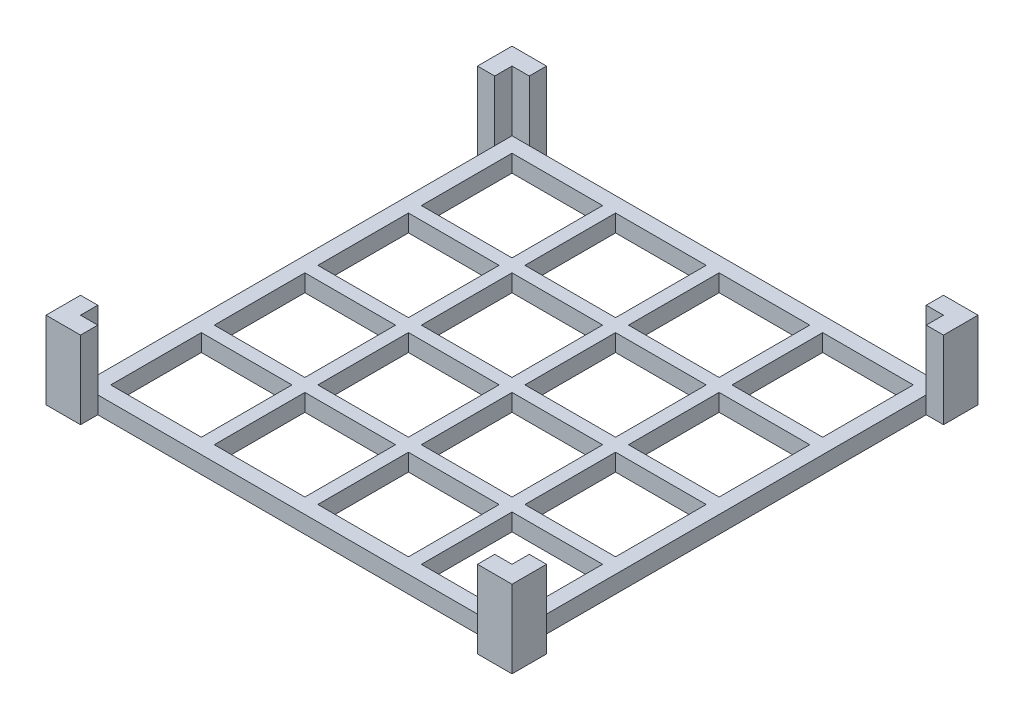
SolidWorks part; units mm, degrees
ref_plane "Front Plane" through (0, 0, 0) normal (0, 0, 1) x (1, 0, 0)
ref_plane "Top Plane" through (0, 0, 0) normal (0, 1, 0) x (1, 0, 0)
ref_plane "Right Plane" through (0, 0, 0) normal (1, 0, 0) x (0, 0, -1)
sketch "Sketch1" plane through (0, 0, 0) normal (0, 1, 0) x (1, 0, 0)
  line L1 (-42, 31) -> (-42, 33)
  line L2 (-42, 33) -> (-46, 33)
  line L3 (-46, 33) -> (-46, 29)
  line L4 (-46, 29) -> (-44, 29)
  line L5 (-44, 29) -> (-44, 31)
  line L6 (4, 33) -> (4, 31)
  line L7 (4, 31) -> (6, 31)
  line L8 (6, 29) -> (8, 29)
  line L9 (-19.75, 29.25) -> (-30.25, 29.25)
  line L10 (-19.75, 29.25) -> (-19.75, 18.75)
  line L11 (-19.75, 18.75) -> (-30.25, 18.75)
  line L12 (-30.25, 29.25) -> (-30.25, 18.75)
  line L13 (-19.75, 29.25) -> (-30.25, 18.75) construction
  line L14 (-19.75, 18.75) -> (-30.25, 29.25) construction
  line L15 (-31.75, 17.25) -> (-42.25, 17.25)
  line L16 (-31.75, 17.25) -> (-31.75, 6.75)
  line L17 (8, 29) -> (8, 33)
  line L18 (-42, 29) -> (-32, 29) construction
  line L19 (-42, 29) -> (-42, 19) construction
  line L20 (-42, 19) -> (-32, 19) construction
  line L21 (-32, 29) -> (-32, 19) construction
  line L22 (-30, 29) -> (-20, 29) construction
  line L23 (-30, 29) -> (-30, 19) construction
  line L24 (-30, 19) -> (-20, 19) construction
  line L25 (-20, 29) -> (-20, 19) construction
  line L26 (-18, 29) -> (-8, 29) construction
  line L27 (-18, 29) -> (-18, 19) construction
  line L28 (-18, 19) -> (-8, 19) construction
  line L29 (-8, 29) -> (-8, 19) construction
  line L30 (-6, 29) -> (4, 29) construction
  line L31 (-6, 29) -> (-6, 19) construction
  line L32 (-6, 19) -> (4, 19) construction
  line L33 (4, 29) -> (4, 19) construction
  line L34 (-32, 17) -> (-42, 17) construction
  line L35 (-32, 17) -> (-32, 7) construction
  line L36 (-32, 7) -> (-42, 7) construction
  line L37 (-42, 17) -> (-42, 7) construction
  line L38 (-30, 17) -> (-20, 17) construction
  line L39 (-30, 17) -> (-30, 7) construction
  line L40 (-30, 7) -> (-20, 7) construction
  line L41 (-20, 17) -> (-20, 7) construction
  line L42 (-18, 7) -> (-8, 7) construction
  line L43 (-18, 7) -> (-18, 17) construction
  line L44 (-18, 17) -> (-8, 17) construction
  line L45 (-8, 7) -> (-8, 17) construction
  line L46 (-6, 17) -> (4, 17) construction
  line L47 (-6, 17) -> (-6, 7) construction
  line L48 (-6, 7) -> (4, 7) construction
  line L49 (4, 17) -> (4, 7) construction
  line L50 (-6, 5) -> (4, 5) construction
  line L51 (-6, 5) -> (-6, -5) construction
  line L52 (-6, -5) -> (4, -5) construction
  line L53 (4, 5) -> (4, -5) construction
  line L54 (-18, -5) -> (-8, -5) construction
  line L55 (-18, -5) -> (-18, 5) construction
  line L56 (-18, 5) -> (-8, 5) construction
  line L57 (-8, -5) -> (-8, 5) construction
  line L58 (-20, 5) -> (-30, 5) construction
  line L59 (-20, 5) -> (-20, -5) construction
  line L60 (-20, -5) -> (-30, -5) construction
  line L61 (-30, 5) -> (-30, -5) construction
  line L62 (-32, -5) -> (-42, -5) construction
  line L63 (-32, -5) -> (-32, 5) construction
  line L64 (-32, 5) -> (-42, 5) construction
  line L65 (-42, -5) -> (-42, 5) construction
  line L66 (-42, -7) -> (-32, -7) construction
  line L67 (-42, -7) -> (-42, -17) construction
  line L68 (-42, -17) -> (-32, -17) construction
  line L69 (-32, -7) -> (-32, -17) construction
  line L70 (-30, -7) -> (-20, -7) construction
  line L71 (-30, -7) -> (-30, -17) construction
  line L72 (-30, -17) -> (-20, -17) construction
  line L73 (-20, -7) -> (-20, -17) construction
  line L74 (-18, -7) -> (-8, -7) construction
  line L75 (-18, -7) -> (-18, -17) construction
  line L76 (-18, -17) -> (-8, -17) construction
  line L77 (-8, -7) -> (-8, -17) construction
  line L78 (-6, -7) -> (4, -7) construction
  line L79 (-6, -7) -> (-6, -17) construction
  line L80 (-6, -17) -> (4, -17) construction
  line L81 (4, -7) -> (4, -17) construction
  line L82 (-44, 31) -> (6, 31)
  line L83 (-44, 31) -> (-44, -19)
  line L84 (-44, -19) -> (6, -19)
  line L85 (6, 31) -> (6, -19)
  line L86 (8, 33) -> (4, 33)
  line L87 (4, -19) -> (4, -21)
  line L88 (4, -21) -> (8, -21)
  line L89 (8, -21) -> (8, -17)
  line L90 (8, -17) -> (6, -17)
  line L91 (6, -17) -> (6, -19)
  line L92 (-42, -21) -> (-46, -21)
  line L93 (-46, -21) -> (-46, -17)
  line L94 (-46, -17) -> (-44, -17)
  line L95 (-44, -17) -> (-44, -19)
  line L96 (-42, -19) -> (-42, -21)
  line L97 (-31.75, 6.75) -> (-42.25, 6.75)
  line L98 (-31.75, 29.25) -> (-42.25, 29.25)
  line L99 (-31.75, 29.25) -> (-31.75, 18.75)
  line L100 (-31.75, 18.75) -> (-42.25, 18.75)
  line L101 (-42.25, 29.25) -> (-42.25, 18.75)
  line L102 (-42.25, 17.25) -> (-42.25, 6.75)
  line L103 (-31.75, 17.25) -> (-42.25, 6.75) construction
  line L104 (-31.75, 6.75) -> (-42.25, 17.25) construction
  line L105 (-7.75, 29.25) -> (-18.25, 29.25)
  line L106 (-7.75, 29.25) -> (-7.75, 18.75)
  line L107 (-7.75, 18.75) -> (-18.25, 18.75)
  line L108 (-18.25, 29.25) -> (-18.25, 18.75)
  line L109 (-7.75, 29.25) -> (-18.25, 18.75) construction
  line L110 (-7.75, 18.75) -> (-18.25, 29.25) construction
  line L111 (4.25, 29.25) -> (-6.25, 29.25)
  line L112 (4.25, 29.25) -> (4.25, 18.75)
  line L113 (4.25, 18.75) -> (-6.25, 18.75)
  line L114 (-6.25, 29.25) -> (-6.25, 18.75)
  line L115 (4.25, 29.25) -> (-6.25, 18.75) construction
  line L116 (4.25, 18.75) -> (-6.25, 29.25) construction
  line L117 (-31.75, 5.25) -> (-42.25, 5.25)
  line L118 (-31.75, 5.25) -> (-31.75, -5.25)
  line L119 (-31.75, -5.25) -> (-42.25, -5.25)
  line L120 (-42.25, 5.25) -> (-42.25, -5.25)
  line L121 (-31.75, 5.25) -> (-42.25, -5.25) construction
  line L122 (-31.75, -5.25) -> (-42.25, 5.25) construction
  line L123 (-31.75, -6.75) -> (-42.25, -6.75)
  line L124 (-31.75, -6.75) -> (-31.75, -17.25)
  line L125 (-31.75, -17.25) -> (-42.25, -17.25)
  line L126 (-42.25, -6.75) -> (-42.25, -17.25)
  line L127 (-31.75, -6.75) -> (-42.25, -17.25) construction
  line L128 (-31.75, -17.25) -> (-42.25, -6.75) construction
  line L129 (-19.75, 17.25) -> (-30.25, 17.25)
  line L130 (-19.75, 17.25) -> (-19.75, 6.75)
  line L131 (-19.75, 6.75) -> (-30.25, 6.75)
  line L132 (-30.25, 17.25) -> (-30.25, 6.75)
  line L133 (-19.75, 17.25) -> (-30.25, 6.75) construction
  line L134 (-19.75, 6.75) -> (-30.25, 17.25) construction
  line L135 (-19.75, 5.25) -> (-30.25, 5.25)
  line L136 (-19.75, 5.25) -> (-19.75, -5.25)
  line L137 (-19.75, -5.25) -> (-30.25, -5.25)
  line L138 (-30.25, 5.25) -> (-30.25, -5.25)
  line L139 (-19.75, 5.25) -> (-30.25, -5.25) construction
  line L140 (-19.75, -5.25) -> (-30.25, 5.25) construction
  line L141 (-7.75, 17.25) -> (-18.25, 17.25)
  line L142 (-7.75, 17.25) -> (-7.75, 6.75)
  line L143 (-7.75, 6.75) -> (-18.25, 6.75)
  line L144 (-18.25, 17.25) -> (-18.25, 6.75)
  line L145 (-7.75, 17.25) -> (-18.25, 6.75) construction
  line L146 (-7.75, 6.75) -> (-18.25, 17.25) construction
  line L147 (4.25, 17.25) -> (-6.25, 17.25)
  line L148 (4.25, 17.25) -> (4.25, 6.75)
  line L149 (4.25, 6.75) -> (-6.25, 6.75)
  line L150 (-6.25, 17.25) -> (-6.25, 6.75)
  line L151 (4.25, 17.25) -> (-6.25, 6.75) construction
  line L152 (4.25, 6.75) -> (-6.25, 17.25) construction
  line L153 (-7.75, 5.25) -> (-18.25, 5.25)
  line L154 (-7.75, 5.25) -> (-7.75, -5.25)
  line L155 (-7.75, -5.25) -> (-18.25, -5.25)
  line L156 (-18.25, 5.25) -> (-18.25, -5.25)
  line L157 (-7.75, 5.25) -> (-18.25, -5.25) construction
  line L158 (-7.75, -5.25) -> (-18.25, 5.25) construction
  line L159 (4.25, 5.25) -> (-6.25, 5.25)
  line L160 (4.25, 5.25) -> (4.25, -5.25)
  line L161 (4.25, -5.25) -> (-6.25, -5.25)
  line L162 (-6.25, 5.25) -> (-6.25, -5.25)
  line L163 (4.25, 5.25) -> (-6.25, -5.25) construction
  line L164 (4.25, -5.25) -> (-6.25, 5.25) construction
  line L165 (-19.75, -6.75) -> (-30.25, -6.75)
  line L166 (-19.75, -6.75) -> (-19.75, -17.25)
  line L167 (-19.75, -17.25) -> (-30.25, -17.25)
  line L168 (-30.25, -6.75) -> (-30.25, -17.25)
  line L169 (-19.75, -6.75) -> (-30.25, -17.25) construction
  line L170 (-19.75, -17.25) -> (-30.25, -6.75) construction
  line L171 (-7.75, -6.75) -> (-18.25, -6.75)
  line L172 (-7.75, -6.75) -> (-7.75, -17.25)
  line L173 (-7.75, -17.25) -> (-18.25, -17.25)
  line L174 (-18.25, -6.75) -> (-18.25, -17.25)
  line L175 (-7.75, -6.75) -> (-18.25, -17.25) construction
  line L176 (-7.75, -17.25) -> (-18.25, -6.75) construction
  line L177 (4.25, -6.75) -> (-6.25, -6.75)
  line L178 (4.25, -6.75) -> (4.25, -17.25)
  line L179 (4.25, -17.25) -> (-6.25, -17.25)
  line L180 (-6.25, -6.75) -> (-6.25, -17.25)
  line L181 (4.25, -6.75) -> (-6.25, -17.25) construction
  line L182 (4.25, -17.25) -> (-6.25, -6.75) construction
  point P1 (-12, 12)
  point P3 (-12, 0)
  point P8 (-24, 0)
  point P10 (0, 24)
  point P11 (-24, 12)
  point P12 (0, 12)
  point P13 (0, -12)
  point P14 (-12, -12)
  point P16 (-24, -12)
  point P19 (-36, 12)
  point P21 (-36, 24)
  point P22 (-24, 24)
  point P23 (-12, 24)
  point P24 (-36, 0)
  point P25 (-36, -12)
  point P26 (-25, 24)
  point P28 (-13, 24)
  point P32 (8, 29)
  point P34 (4, 33)
  point P35 (8, 33)
  point P36 (-46, -19)
  point P37 (-46, -21)
  point P38 (-42, -21)
  point P39 (4, -21)
  point P40 (8, -21)
  point P41 (8, -17)
  point P48 (-1, 24)
  point P49 (-13, 12)
  point P50 (-1, 12)
  point P51 (-25, 12)
  point P52 (-37, 12)
  point P54 (-37, 0)
  point P55 (-25, 0)
  point P56 (-13, 0)
  point P60 (-1, 0)
  point P62 (-1, -12)
  point P63 (-13, -12)
  point P64 (-25, -12)
  point P65 (-37, -12)
  point P66 (-25, 24)
  point P136 (-37, 12)
  point P144 (-13, 24)
  point P149 (-1, 24)
  point P154 (-37, 0)
  point P159 (-37, -12)
  point P164 (-25, 12)
  point P169 (-25, 0)
  point P174 (-13, 12)
  point P179 (-1, 12)
  point P184 (-13, 0)
  point P189 (-1, 0)
  point P194 (-25, -12)
  point P199 (-13, -12)
  point P204 (-1, -12)
  line B0 (-0.1035, 1.9813) -> (-3.7918, 1.315) construction
  line B1 (-3.7918, -1.315) -> (-0.1035, -1.9813) construction
  arc B2 (-3.9397, 1.2764) -> (-3.9397, -1.2764) centre (-3.5, 0) ccw construction
  arc B3 (0.1486, 1.9945) -> (0.1486, -1.9945) centre (0, 0) cw construction
  arc B4 (-3.9397, 1.2764) -> (-3.7918, 1.315) centre (-3.614, 0.3309) cw construction
  arc B5 (-3.7918, -1.315) -> (-3.9397, -1.2764) centre (-3.614, -0.3309) cw construction
  arc B6 (0.1486, 1.9945) -> (-0.1035, 1.9813) centre (0.0743, 0.9972) ccw construction
  arc B7 (0.1486, -1.9945) -> (-0.1035, -1.9813) centre (0.0743, -0.9972) cw construction
  line B8 (-12.1035, 1.9813) -> (-15.7918, 1.315) construction
  line B9 (-15.7918, -1.315) -> (-12.1035, -1.9813) construction
  arc B10 (-15.9397, 1.2764) -> (-15.9397, -1.2764) centre (-15.5, 0) ccw construction
  arc B11 (-11.8514, 1.9945) -> (-11.8514, -1.9945) centre (-12, 0) cw construction
  arc B12 (-15.9397, 1.2764) -> (-15.7918, 1.315) centre (-15.614, 0.3309) cw construction
  arc B13 (-15.7918, -1.315) -> (-15.9397, -1.2764) centre (-15.614, -0.3309) cw construction
  arc B14 (-11.8514, 1.9945) -> (-12.1035, 1.9813) centre (-11.9257, 0.9972) ccw construction
  arc B15 (-11.8514, -1.9945) -> (-12.1035, -1.9813) centre (-11.9257, -0.9972) cw construction
  line B16 (-24.1035, 1.9813) -> (-27.7918, 1.315) construction
  line B17 (-27.7918, -1.315) -> (-24.1035, -1.9813) construction
  arc B18 (-27.9397, 1.2764) -> (-27.9397, -1.2764) centre (-27.5, 0) ccw construction
  arc B19 (-23.8514, 1.9945) -> (-23.8514, -1.9945) centre (-24, 0) cw construction
  arc B20 (-27.9397, 1.2764) -> (-27.7918, 1.315) centre (-27.614, 0.3309) cw construction
  arc B21 (-27.7918, -1.315) -> (-27.9397, -1.2764) centre (-27.614, -0.3309) cw construction
  arc B22 (-23.8514, 1.9945) -> (-24.1035, 1.9813) centre (-23.9257, 0.9972) ccw construction
  arc B23 (-23.8514, -1.9945) -> (-24.1035, -1.9813) centre (-23.9257, -0.9972) cw construction
  line B24 (-0.1035, 13.9813) -> (-3.7918, 13.315) construction
  line B25 (-3.7918, 10.685) -> (-0.1035, 10.0187) construction
  arc B26 (-3.9397, 13.2764) -> (-3.9397, 10.7236) centre (-3.5, 12) ccw construction
  arc B27 (0.1486, 13.9945) -> (0.1486, 10.0055) centre (0, 12) cw construction
  arc B28 (-3.9397, 13.2764) -> (-3.7918, 13.315) centre (-3.614, 12.3309) cw construction
  arc B29 (-3.7918, 10.685) -> (-3.9397, 10.7236) centre (-3.614, 11.6691) cw construction
  arc B30 (0.1486, 13.9945) -> (-0.1035, 13.9813) centre (0.0743, 12.9972) ccw construction
  arc B31 (0.1486, 10.0055) -> (-0.1035, 10.0187) centre (0.0743, 11.0028) cw construction
  line B32 (-12.1035, 13.9813) -> (-15.7918, 13.315) construction
  line B33 (-15.7918, 10.685) -> (-12.1035, 10.0187) construction
  arc B34 (-15.9397, 13.2764) -> (-15.9397, 10.7236) centre (-15.5, 12) ccw construction
  arc B35 (-11.8514, 13.9945) -> (-11.8514, 10.0055) centre (-12, 12) cw construction
  arc B36 (-15.9397, 13.2764) -> (-15.7918, 13.315) centre (-15.614, 12.3309) cw construction
  arc B37 (-15.7918, 10.685) -> (-15.9397, 10.7236) centre (-15.614, 11.6691) cw construction
  arc B38 (-11.8514, 13.9945) -> (-12.1035, 13.9813) centre (-11.9257, 12.9972) ccw construction
  arc B39 (-11.8514, 10.0055) -> (-12.1035, 10.0187) centre (-11.9257, 11.0028) cw construction
  line B40 (-24.1035, 13.9813) -> (-27.7918, 13.315) construction
  line B41 (-27.7918, 10.685) -> (-24.1035, 10.0187) construction
  arc B42 (-27.9397, 13.2764) -> (-27.9397, 10.7236) centre (-27.5, 12) ccw construction
  arc B43 (-23.8514, 13.9945) -> (-23.8514, 10.0055) centre (-24, 12) cw construction
  arc B44 (-27.9397, 13.2764) -> (-27.7918, 13.315) centre (-27.614, 12.3309) cw construction
  arc B45 (-27.7918, 10.685) -> (-27.9397, 10.7236) centre (-27.614, 11.6691) cw construction
  arc B46 (-23.8514, 13.9945) -> (-24.1035, 13.9813) centre (-23.9257, 12.9972) ccw construction
  arc B47 (-23.8514, 10.0055) -> (-24.1035, 10.0187) centre (-23.9257, 11.0028) cw construction
  line B48 (-12.1035, -10.0187) -> (-15.7918, -10.685) construction
  line B49 (-15.7918, -13.315) -> (-12.1035, -13.9813) construction
  arc B50 (-15.9397, -10.7236) -> (-15.9397, -13.2764) centre (-15.5, -12) ccw construction
  arc B51 (-11.8514, -10.0055) -> (-11.8514, -13.9945) centre (-12, -12) cw construction
  arc B52 (-15.9397, -10.7236) -> (-15.7918, -10.685) centre (-15.614, -11.6691) cw construction
  arc B53 (-15.7918, -13.315) -> (-15.9397, -13.2764) centre (-15.614, -12.3309) cw construction
  arc B54 (-11.8514, -10.0055) -> (-12.1035, -10.0187) centre (-11.9257, -11.0028) ccw construction
  arc B55 (-11.8514, -13.9945) -> (-12.1035, -13.9813) centre (-11.9257, -12.9972) cw construction
  line B56 (-0.1035, -10.0187) -> (-3.7918, -10.685) construction
  line B57 (-3.7918, -13.315) -> (-0.1035, -13.9813) construction
  arc B58 (-3.9397, -10.7236) -> (-3.9397, -13.2764) centre (-3.5, -12) ccw construction
  arc B59 (0.1486, -10.0055) -> (0.1486, -13.9945) centre (0, -12) cw construction
  arc B60 (-3.9397, -10.7236) -> (-3.7918, -10.685) centre (-3.614, -11.6691) cw construction
  arc B61 (-3.7918, -13.315) -> (-3.9397, -13.2764) centre (-3.614, -12.3309) cw construction
  arc B62 (0.1486, -10.0055) -> (-0.1035, -10.0187) centre (0.0743, -11.0028) ccw construction
  arc B63 (0.1486, -13.9945) -> (-0.1035, -13.9813) centre (0.0743, -12.9972) cw construction
  line B64 (-24.1035, -10.0187) -> (-27.7918, -10.685) construction
  line B65 (-27.7918, -13.315) -> (-24.1035, -13.9813) construction
  arc B66 (-27.9397, -10.7236) -> (-27.9397, -13.2764) centre (-27.5, -12) ccw construction
  arc B67 (-23.8514, -10.0055) -> (-23.8514, -13.9945) centre (-24, -12) cw construction
  arc B68 (-27.9397, -10.7236) -> (-27.7918, -10.685) centre (-27.614, -11.6691) cw construction
  arc B69 (-27.7918, -13.315) -> (-27.9397, -13.2764) centre (-27.614, -12.3309) cw construction
  arc B70 (-23.8514, -10.0055) -> (-24.1035, -10.0187) centre (-23.9257, -11.0028) ccw construction
  arc B71 (-23.8514, -13.9945) -> (-24.1035, -13.9813) centre (-23.9257, -12.9972) cw construction
  line B72 (-0.1035, 25.9813) -> (-3.7918, 25.315) construction
  line B73 (-3.7918, 22.685) -> (-0.1035, 22.0187) construction
  arc B74 (-3.9397, 25.2764) -> (-3.9397, 22.7236) centre (-3.5, 24) ccw construction
  arc B75 (0.1486, 25.9945) -> (0.1486, 22.0055) centre (0, 24) cw construction
  arc B76 (-3.9397, 25.2764) -> (-3.7918, 25.315) centre (-3.614, 24.3309) cw construction
  arc B77 (-3.7918, 22.685) -> (-3.9397, 22.7236) centre (-3.614, 23.6691) cw construction
  arc B78 (0.1486, 25.9945) -> (-0.1035, 25.9813) centre (0.0743, 24.9972) ccw construction
  arc B79 (0.1486, 22.0055) -> (-0.1035, 22.0187) centre (0.0743, 23.0028) cw construction
  line B80 (-12.1035, 25.9813) -> (-15.7918, 25.315) construction
  line B81 (-15.7918, 22.685) -> (-12.1035, 22.0187) construction
  arc B82 (-15.9397, 25.2764) -> (-15.9397, 22.7236) centre (-15.5, 24) ccw construction
  arc B83 (-11.8514, 25.9945) -> (-11.8514, 22.0055) centre (-12, 24) cw construction
  arc B84 (-15.9397, 25.2764) -> (-15.7918, 25.315) centre (-15.614, 24.3309) cw construction
  arc B85 (-15.7918, 22.685) -> (-15.9397, 22.7236) centre (-15.614, 23.6691) cw construction
  arc B86 (-11.8514, 25.9945) -> (-12.1035, 25.9813) centre (-11.9257, 24.9972) ccw construction
  arc B87 (-11.8514, 22.0055) -> (-12.1035, 22.0187) centre (-11.9257, 23.0028) cw construction
  line B88 (-24.1035, 25.9813) -> (-27.7918, 25.315) construction
  line B89 (-27.7918, 22.685) -> (-24.1035, 22.0187) construction
  arc B90 (-27.9397, 25.2764) -> (-27.9397, 22.7236) centre (-27.5, 24) ccw construction
  arc B91 (-23.8514, 25.9945) -> (-23.8514, 22.0055) centre (-24, 24) cw construction
  arc B92 (-27.9397, 25.2764) -> (-27.7918, 25.315) centre (-27.614, 24.3309) cw construction
  arc B93 (-27.7918, 22.685) -> (-27.9397, 22.7236) centre (-27.614, 23.6691) cw construction
  arc B94 (-23.8514, 25.9945) -> (-24.1035, 25.9813) centre (-23.9257, 24.9972) ccw construction
  arc B95 (-23.8514, 22.0055) -> (-24.1035, 22.0187) centre (-23.9257, 23.0028) cw construction
  line B96 (-36.1035, -10.0187) -> (-39.7918, -10.685) construction
  line B97 (-39.7918, -13.315) -> (-36.1035, -13.9813) construction
  arc B98 (-39.9397, -10.7236) -> (-39.9397, -13.2764) centre (-39.5, -12) ccw construction
  arc B99 (-35.8514, -10.0055) -> (-35.8514, -13.9945) centre (-36, -12) cw construction
  arc B100 (-39.9397, -10.7236) -> (-39.7918, -10.685) centre (-39.614, -11.6691) cw construction
  arc B101 (-39.7918, -13.315) -> (-39.9397, -13.2764) centre (-39.614, -12.3309) cw construction
  arc B102 (-35.8514, -10.0055) -> (-36.1035, -10.0187) centre (-35.9257, -11.0028) ccw construction
  arc B103 (-35.8514, -13.9945) -> (-36.1035, -13.9813) centre (-35.9257, -12.9972) cw construction
  line B104 (-36.1035, 25.9813) -> (-39.7918, 25.315) construction
  line B105 (-39.7918, 22.685) -> (-36.1035, 22.0187) construction
  arc B106 (-39.9397, 25.2764) -> (-39.9397, 22.7236) centre (-39.5, 24) ccw construction
  arc B107 (-35.8514, 25.9945) -> (-35.8514, 22.0055) centre (-36, 24) cw construction
  arc B108 (-39.9397, 25.2764) -> (-39.7918, 25.315) centre (-39.614, 24.3309) cw construction
  arc B109 (-39.7918, 22.685) -> (-39.9397, 22.7236) centre (-39.614, 23.6691) cw construction
  arc B110 (-35.8514, 25.9945) -> (-36.1035, 25.9813) centre (-35.9257, 24.9972) ccw construction
  arc B111 (-35.8514, 22.0055) -> (-36.1035, 22.0187) centre (-35.9257, 23.0028) cw construction
  line B112 (-36.1035, 1.9813) -> (-39.7918, 1.315) construction
  line B113 (-39.7918, -1.315) -> (-36.1035, -1.9813) construction
  arc B114 (-39.9397, 1.2764) -> (-39.9397, -1.2764) centre (-39.5, 0) ccw construction
  arc B115 (-35.8514, 1.9945) -> (-35.8514, -1.9945) centre (-36, 0) cw construction
  arc B116 (-39.9397, 1.2764) -> (-39.7918, 1.315) centre (-39.614, 0.3309) cw construction
  arc B117 (-39.7918, -1.315) -> (-39.9397, -1.2764) centre (-39.614, -0.3309) cw construction
  arc B118 (-35.8514, 1.9945) -> (-36.1035, 1.9813) centre (-35.9257, 0.9972) ccw construction
  arc B119 (-35.8514, -1.9945) -> (-36.1035, -1.9813) centre (-35.9257, -0.9972) cw construction
  line B120 (-36.1035, 13.9813) -> (-39.7918, 13.315) construction
  line B121 (-39.7918, 10.685) -> (-36.1035, 10.0187) construction
  arc B122 (-39.9397, 13.2764) -> (-39.9397, 10.7236) centre (-39.5, 12) ccw construction
  arc B123 (-35.8514, 13.9945) -> (-35.8514, 10.0055) centre (-36, 12) cw construction
  arc B124 (-39.9397, 13.2764) -> (-39.7918, 13.315) centre (-39.614, 12.3309) cw construction
  arc B125 (-39.7918, 10.685) -> (-39.9397, 10.7236) centre (-39.614, 11.6691) cw construction
  arc B126 (-35.8514, 13.9945) -> (-36.1035, 13.9813) centre (-35.9257, 12.9972) ccw construction
  arc B127 (-35.8514, 10.0055) -> (-36.1035, 10.0187) centre (-35.9257, 11.0028) cw construction
sketch_block_instance "Block1-4"
sketch_block "Block1"
sketch_block_instance "Block1-6"
sketch_block_instance "Block1-7"
sketch_block_instance "Block1-8"
sketch_block_instance "Block1-9"
sketch_block_instance "Block1-10"
sketch_block_instance "Block1-14"
sketch_block_instance "Block1-15"
sketch_block_instance "Block1-16"
sketch_block_instance "Block1-17"
sketch_block_instance "Block1-18"
sketch_block_instance "Block1-19"
sketch_block_instance "Block1-20"
sketch_block_instance "Block1-21"
sketch_block_instance "Block1-22"
sketch_block_instance "Block1-23"
extrude "Boss-Extrude1" add sketch "Sketch1" along normal blind 2 contours L85 L7 L82 L5 L83 L84 L180 L177 L178 L179 L174 L171 L172 L173 L168 L165 L166 L167 L162 L159 L160 L161 L156 L153 L154 L155 L150 L147 L148 L149 L144 L141 L142 L143 L138 L135 L136 region at (-19, 0, -6)
extrude "Boss-Extrude2" add sketch "Sketch1<32>" along normal blind 9 contours L17 L86 L6 L7 L85 L8 | L5 L82 L1 L2 L3 L4 | L96 L84 L83 L94 L93 L92 | L89 L90 L85 L84 L87 L88 region at (-44.3333, 0, -31.3333) region at (6.3333, 0, -31.3333) region at (-44.3333, 0, 19.3333) region at (6.3333, 0, 19.3333)
sketch "Sketch1<32>" plane through (0, 0, 0) normal (0, 1, 0) x (1, 0, 0) same geometry as "Sketch1"
